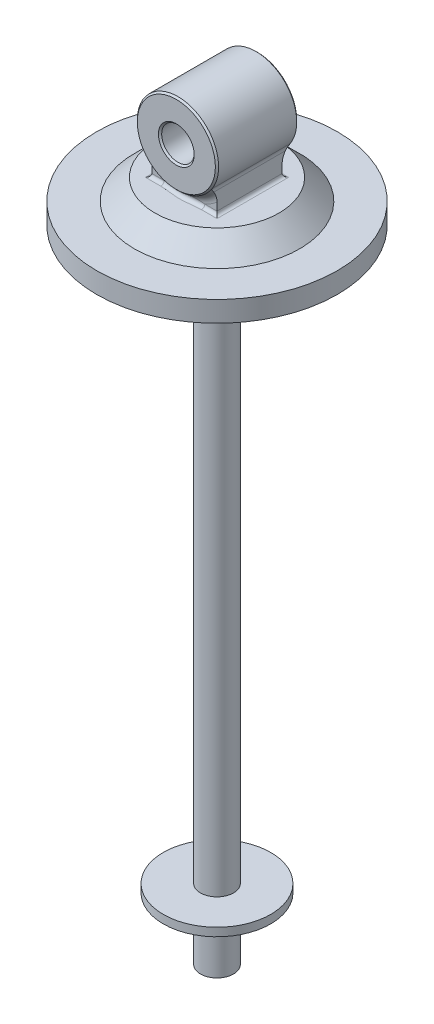
SolidWorks part; units mm, degrees
ref_plane "Plan de face" through (0, 0, 0) normal (0, 0, 1) x (1, 0, 0)
ref_plane "Plan de dessus" through (0, 0, 0) normal (0, 1, 0) x (1, 0, 0)
ref_plane "Plan de droite" through (0, 0, 0) normal (1, 0, 0) x (0, 0, -1)
sketch "Sketch1" plane through (0, 0, 0) normal (0, 1, 0) x (1, 0, 0)
  circle A0 centre (0, 0) radius 16.51
  circle A1 centre (0, 0) radius 5.08
  dimension "D1" = 33.02
  dimension "D2" = 10.16
extrude "Boss-Extrude1" add sketch "Sketch1" along normal blind 2.54
sketch "Sketch2" plane through (0, 0, 0) normal (0, -1, 0) x (1, 0, 0)
  circle A0 centre (0, 0) radius 5.08 construction
  circle A1 centre (0, 0) radius 5.08
extrude "Boss-Extrude2" add sketch "Sketch2" along normal blind 19.05 separate body
sketch "Sketch3" plane through (0, 0, 0) normal (0, 1, 0) x (1, 0, 0)
  circle A1 centre (0, 0) radius 5.08
  circle A2 centre (0, 0) radius 5.08
  dimension "D1" = 0
extrude "Boss-Extrude5" add sketch "Sketch3" along normal blind 177.8 contours A2
sketch "Sketch5" plane through (0, 177.8, 0) normal (0, 1, 0) x (1, 0, 0)
  circle A0 centre (0, 0) radius 12.7
  dimension "D1" = 25.4
extrude "Boss-Extrude6" add sketch "Sketch5" against normal blind 6.35
sketch "Sketch6" plane through (0, 177.8, 0) normal (0, 1, 0) x (1, 0, 0)
  circle A0 centre (0, 0) radius 37
  dimension "D1" = 74
extrude "Boss-Extrude7" add sketch "Sketch6" along normal blind 6.35
sketch "Sketch7" plane through (0, 184.15, 0) normal (0, 1, 0) x (1, 0, 0)
  circle A0 centre (0, 0) radius 25.4
  dimension "D1" = 50.8
extrude "Boss-Extrude8" add sketch "Sketch7" along normal blind 6.35 draft 45
sketch "Sketch10" plane through (0, 190.5, 0) normal (0, 1, 0) x (1, 0, 0)
  line L1 (10, -10) -> (-10, -10)
  line L2 (10, -10) -> (10, 10)
  line L3 (10, 10) -> (-10, 10)
  line L4 (-10, -10) -> (-10, 10)
  line L5 (10, -10) -> (-10, 10) construction
  line L6 (10, 10) -> (-10, -10) construction
  point P0 (0, 0)
  dimension "D1" = 20
extrude "Boss-Extrude9" add sketch "Sketch10" along normal blind 20
sketch "Sketch11" plane through (0, 0, 0) normal (0, 0, 1) x (1, 0, 0)
  line L0 (-10, 210.5) -> (10, 210.5) construction
  circle A0 centre (0, 205.5) radius 12.5
  point P2 (0, 210.5)
  dimension "D1" = 25
  dimension "D2" = 5
extrude "Boss-Extrude10" add sketch "Sketch11" along normal mid plane 25
sketch "Sketch12" plane through (0, 0, 12.5) normal (0, 0, 1) x (1, 0, 0)
  circle A0 centre (0, 205.5) radius 5
  dimension "D1" = 10
extrude "Cut-Extrude1" cut sketch "Sketch12" against normal blind 25
chamfer "Chamfer1" distance 0.5 angle 45 4 edges at (12.5, 205.5, -12.5) (5, 205.5, -12.5) (12.5, 205.5, 12.5) (5, 205.5, 12.5)
fillet "Fillet1" radius 3 4 edges at (0, 193, 10) (-10, 198, 0) (0, 193, -10) (10, 198, 0)
fillet "Fillet2" radius 1 8 edges at (6.578, 190.5, 10) (0, 190.5, 10.018) (-6.578, 190.5, -10) (0, 190.5, -10.018) (6.578, 190.5, -10) (10, 190.5, 0) (-6.578, 190.5, 10) (-10, 190.5, 0)
